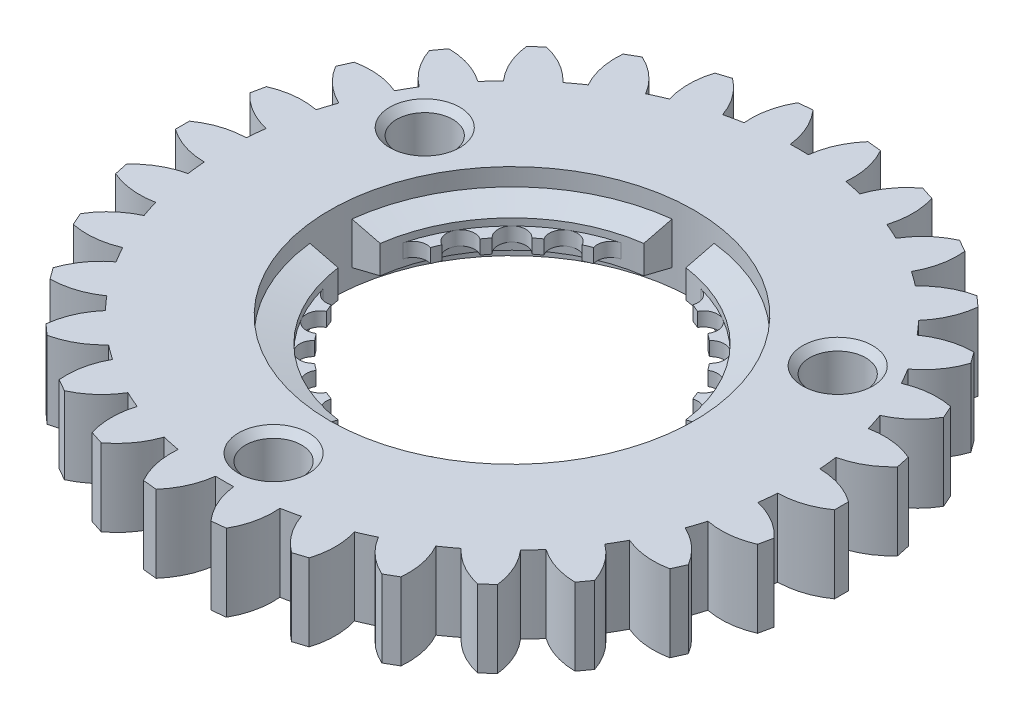
SolidWorks part; units mm, degrees
ref_plane "前视基准面" through (0, 0, 0) normal (0, 0, 1) x (1, 0, 0)
ref_plane "上视基准面" through (0, 0, 0) normal (0, 1, 0) x (1, 0, 0)
ref_plane "右视基准面" through (0, 0, 0) normal (1, 0, 0) x (0, 0, -1)
sketch "草图1" plane through (0, 0, 0) normal (0, 1, 0) x (1, 0, 0)
  circle A0 centre (0, 0) radius 20.5
  dimension "D1" = 41
extrude "凸台-拉伸1" add sketch "草图1" along normal blind 5.5
sketch "草图2" plane through (0, 0, 0) normal (0, 1, 0) x (1, 0, 0)
  line L0 (0, 0) -> (-20.5, 0) construction
  line L1 (-20.5, 0) -> (-23.5, 0) construction
  line L2 (-23.5, 0.5) -> (-23.5, -0.5)
  line L3 (-20.5, 0) -> (-20.5, -1.5) construction
  line L4 (-22, 0) -> (-22, -1.25) construction
  line L5 (-22.8825, 5.375) -> (-23.0904, 4.3969)
  line L6 (-21.2649, 10.0151) -> (-21.6717, 9.1015)
  line L7 (-18.718, 14.2175) -> (-19.3058, 13.4084)
  line L8 (-15.353, 17.7985) -> (-16.0961, 17.1293)
  line L9 (-11.317, 20.6016) -> (-12.183, 20.1016)
  line L10 (-6.7864, 22.5043) -> (-7.7374, 22.1953)
  line L11 (-1.9592, 23.4235) -> (-2.9537, 23.319)
  line L12 (2.9537, 23.319) -> (1.9592, 23.4235)
  line L13 (7.7374, 22.1953) -> (6.7864, 22.5043)
  line L14 (12.183, 20.1016) -> (11.317, 20.6016)
  line L15 (16.0961, 17.1293) -> (15.353, 17.7985)
  line L16 (19.3058, 13.4084) -> (18.718, 14.2175)
  line L17 (21.6717, 9.1015) -> (21.2649, 10.0151)
  line L18 (23.0904, 4.3969) -> (22.8825, 5.375)
  line L19 (23.5, -0.5) -> (23.5, 0.5)
  line L20 (22.8825, -5.375) -> (23.0904, -4.3969)
  line L21 (21.2649, -10.0151) -> (21.6717, -9.1015)
  line L22 (18.718, -14.2175) -> (19.3058, -13.4084)
  line L23 (15.353, -17.7985) -> (16.0961, -17.1293)
  line L24 (11.317, -20.6016) -> (12.183, -20.1016)
  line L25 (6.7864, -22.5043) -> (7.7374, -22.1953)
  line L26 (1.9592, -23.4235) -> (2.9537, -23.319)
  line L27 (-2.9537, -23.319) -> (-1.9592, -23.4235)
  line L28 (-7.7374, -22.1953) -> (-6.7864, -22.5043)
  line L29 (-12.183, -20.1016) -> (-11.317, -20.6016)
  line L30 (-16.0961, -17.1293) -> (-15.353, -17.7985)
  line L31 (-19.3058, -13.4084) -> (-18.718, -14.2175)
  line L32 (-21.6717, -9.1015) -> (-21.2649, -10.0151)
  line L33 (-23.0904, -4.3969) -> (-22.8825, -5.375)
  arc A0 (-20.445, 1.5) -> (-20.445, -1.5) centre (0, 0) ccw
  arc A1 (-23.5, -0.5) -> (-20.445, -1.5) centre (-20.3801, 3.8648) ccw
  arc A2 (-23.5, 0.5) -> (-20.445, 1.5) centre (-20.3801, -3.8648) cw
  arc A3 (-22.8825, 5.375) -> (-19.6864, 5.718) centre (-20.7383, 0.4569) cw
  arc A4 (-23.0904, 4.3969) -> (-20.3101, 2.7835) centre (-19.1312, 8.0176) ccw
  arc A5 (-19.6864, 5.718) -> (-20.3101, 2.7835) centre (0, 0) ccw
  arc A6 (-21.2649, 10.0151) -> (-18.0674, 9.6861) centre (-20.1901, 4.7586) cw
  arc A7 (-21.6717, 9.1015) -> (-19.2876, 6.9454) centre (-17.0462, 11.82) ccw
  arc A8 (-18.0674, 9.6861) -> (-19.2876, 6.9454) centre (0, 0) ccw
  arc A9 (-18.718, 14.2175) -> (-15.6587, 13.2308) centre (-18.7595, 8.8524) cw
  arc A10 (-19.3058, 13.4084) -> (-17.4221, 10.8038) centre (-14.2161, 15.1058) ccw
  arc A11 (-15.6587, 13.2308) -> (-17.4221, 10.8038) centre (0, 0) ccw
  arc A12 (-15.353, 17.7985) -> (-12.5657, 16.1973) centre (-16.5091, 12.5593) cw
  arc A13 (-16.0961, 17.1293) -> (-14.7951, 14.1899) centre (-10.7648, 17.7314) ccw
  arc A14 (-12.5657, 16.1973) -> (-14.7951, 14.1899) centre (0, 0) ccw
  arc A15 (-11.317, 20.6016) -> (-8.9235, 18.4559) centre (-13.5371, 15.7172) cw
  arc A16 (-12.183, 20.1016) -> (-11.5216, 16.9559) centre (-6.843, 19.5821) ccw
  arc A17 (-8.9235, 18.4559) -> (-11.5216, 16.9559) centre (0, 0) ccw
  arc A18 (-6.7864, 22.5043) -> (-4.8913, 19.9079) centre (-9.9735, 18.1883) cw
  arc A19 (-7.7374, 22.1953) -> (-7.7445, 18.9809) centre (-2.6221, 20.5769) ccw
  arc A20 (-4.8913, 19.9079) -> (-7.7445, 18.9809) centre (0, 0) ccw
  arc A21 (-1.9592, 23.4235) -> (-0.6453, 20.4898) centre (-5.974, 19.8644) cw
  arc A22 (-2.9537, 23.319) -> (-3.6289, 20.1763) centre (1.7134, 20.6724) ccw
  arc A23 (-0.6453, 20.4898) -> (-3.6289, 20.1763) centre (0, 0) ccw
  arc A24 (2.9537, 23.319) -> (3.6289, 20.1763) centre (-1.7134, 20.6724) cw
  arc A25 (1.9592, 23.4235) -> (0.6453, 20.4898) centre (5.974, 19.8644) ccw
  arc A26 (3.6289, 20.1763) -> (0.6453, 20.4898) centre (0, 0) ccw
  arc A27 (7.7374, 22.1953) -> (7.7445, 18.9809) centre (2.6221, 20.5769) cw
  arc A28 (6.7864, 22.5043) -> (4.8913, 19.9079) centre (9.9735, 18.1883) ccw
  arc A29 (7.7445, 18.9809) -> (4.8913, 19.9079) centre (0, 0) ccw
  arc A30 (12.183, 20.1016) -> (11.5216, 16.9559) centre (6.843, 19.5821) cw
  arc A31 (11.317, 20.6016) -> (8.9235, 18.4559) centre (13.5371, 15.7172) ccw
  arc A32 (11.5216, 16.9559) -> (8.9235, 18.4559) centre (0, 0) ccw
  arc A33 (16.0961, 17.1293) -> (14.7951, 14.1899) centre (10.7648, 17.7314) cw
  arc A34 (15.353, 17.7985) -> (12.5657, 16.1973) centre (16.5091, 12.5593) ccw
  arc A35 (14.7951, 14.1899) -> (12.5657, 16.1973) centre (0, 0) ccw
  arc A36 (19.3058, 13.4084) -> (17.4221, 10.8038) centre (14.2161, 15.1058) cw
  arc A37 (18.718, 14.2175) -> (15.6587, 13.2308) centre (18.7595, 8.8524) ccw
  arc A38 (17.4221, 10.8038) -> (15.6587, 13.2308) centre (0, 0) ccw
  arc A39 (21.6717, 9.1015) -> (19.2876, 6.9454) centre (17.0462, 11.82) cw
  arc A40 (21.2649, 10.0151) -> (18.0674, 9.6861) centre (20.1901, 4.7586) ccw
  arc A41 (19.2876, 6.9454) -> (18.0674, 9.6861) centre (0, 0) ccw
  arc A42 (23.0904, 4.3969) -> (20.3101, 2.7835) centre (19.1312, 8.0176) cw
  arc A43 (22.8825, 5.375) -> (19.6864, 5.718) centre (20.7383, 0.4569) ccw
  arc A44 (20.3101, 2.7835) -> (19.6864, 5.718) centre (0, 0) ccw
  arc A45 (23.5, -0.5) -> (20.445, -1.5) centre (20.3801, 3.8648) cw
  arc A46 (23.5, 0.5) -> (20.445, 1.5) centre (20.3801, -3.8648) ccw
  arc A47 (20.445, -1.5) -> (20.445, 1.5) centre (0, 0) ccw
  arc A48 (22.8825, -5.375) -> (19.6864, -5.718) centre (20.7383, -0.4569) cw
  arc A49 (23.0904, -4.3969) -> (20.3101, -2.7835) centre (19.1312, -8.0176) ccw
  arc A50 (19.6864, -5.718) -> (20.3101, -2.7835) centre (0, 0) ccw
  arc A51 (21.2649, -10.0151) -> (18.0674, -9.6861) centre (20.1901, -4.7586) cw
  arc A52 (21.6717, -9.1015) -> (19.2876, -6.9454) centre (17.0462, -11.82) ccw
  arc A53 (18.0674, -9.6861) -> (19.2876, -6.9454) centre (0, 0) ccw
  arc A54 (18.718, -14.2175) -> (15.6587, -13.2308) centre (18.7595, -8.8524) cw
  arc A55 (19.3058, -13.4084) -> (17.4221, -10.8038) centre (14.2161, -15.1058) ccw
  arc A56 (15.6587, -13.2308) -> (17.4221, -10.8038) centre (0, 0) ccw
  arc A57 (15.353, -17.7985) -> (12.5657, -16.1973) centre (16.5091, -12.5593) cw
  arc A58 (16.0961, -17.1293) -> (14.7951, -14.1899) centre (10.7648, -17.7314) ccw
  arc A59 (12.5657, -16.1973) -> (14.7951, -14.1899) centre (0, 0) ccw
  arc A60 (11.317, -20.6016) -> (8.9235, -18.4559) centre (13.5371, -15.7172) cw
  arc A61 (12.183, -20.1016) -> (11.5216, -16.9559) centre (6.843, -19.5821) ccw
  arc A62 (8.9235, -18.4559) -> (11.5216, -16.9559) centre (0, 0) ccw
  arc A63 (6.7864, -22.5043) -> (4.8913, -19.9079) centre (9.9735, -18.1883) cw
  arc A64 (7.7374, -22.1953) -> (7.7445, -18.9809) centre (2.6221, -20.5769) ccw
  arc A65 (4.8913, -19.9079) -> (7.7445, -18.9809) centre (0, 0) ccw
  arc A66 (1.9592, -23.4235) -> (0.6453, -20.4898) centre (5.974, -19.8644) cw
  arc A67 (2.9537, -23.319) -> (3.6289, -20.1763) centre (-1.7134, -20.6724) ccw
  arc A68 (0.6453, -20.4898) -> (3.6289, -20.1763) centre (0, 0) ccw
  arc A69 (-2.9537, -23.319) -> (-3.6289, -20.1763) centre (1.7134, -20.6724) cw
  arc A70 (-1.9592, -23.4235) -> (-0.6453, -20.4898) centre (-5.974, -19.8644) ccw
  arc A71 (-3.6289, -20.1763) -> (-0.6453, -20.4898) centre (0, 0) ccw
  arc A72 (-7.7374, -22.1953) -> (-7.7445, -18.9809) centre (-2.6221, -20.5769) cw
  arc A73 (-6.7864, -22.5043) -> (-4.8913, -19.9079) centre (-9.9735, -18.1883) ccw
  arc A74 (-7.7445, -18.9809) -> (-4.8913, -19.9079) centre (0, 0) ccw
  arc A75 (-12.183, -20.1016) -> (-11.5216, -16.9559) centre (-6.843, -19.5821) cw
  arc A76 (-11.317, -20.6016) -> (-8.9235, -18.4559) centre (-13.5371, -15.7172) ccw
  arc A77 (-11.5216, -16.9559) -> (-8.9235, -18.4559) centre (0, 0) ccw
  arc A78 (-16.0961, -17.1293) -> (-14.7951, -14.1899) centre (-10.7648, -17.7314) cw
  arc A79 (-15.353, -17.7985) -> (-12.5657, -16.1973) centre (-16.5091, -12.5593) ccw
  arc A80 (-14.7951, -14.1899) -> (-12.5657, -16.1973) centre (0, 0) ccw
  arc A81 (-19.3058, -13.4084) -> (-17.4221, -10.8038) centre (-14.2161, -15.1058) cw
  arc A82 (-18.718, -14.2175) -> (-15.6587, -13.2308) centre (-18.7595, -8.8524) ccw
  arc A83 (-17.4221, -10.8038) -> (-15.6587, -13.2308) centre (0, 0) ccw
  arc A84 (-21.6717, -9.1015) -> (-19.2876, -6.9454) centre (-17.0462, -11.82) cw
  arc A85 (-21.2649, -10.0151) -> (-18.0674, -9.6861) centre (-20.1901, -4.7586) ccw
  arc A86 (-19.2876, -6.9454) -> (-18.0674, -9.6861) centre (0, 0) ccw
  arc A87 (-23.0904, -4.3969) -> (-20.3101, -2.7835) centre (-19.1312, -8.0176) cw
  arc A88 (-22.8825, -5.375) -> (-19.6864, -5.718) centre (-20.7383, -0.4569) ccw
  arc A89 (-20.3101, -2.7835) -> (-19.6864, -5.718) centre (0, 0) ccw
  point P190 (0, 0)
  dimension "D1" = 30
  dimension "D2" = 0.5
  dimension "D4" = 1.25
extrude "凸台-拉伸2" add sketch "草图2" along normal blind 5.5
sketch "草图3" plane through (0, 5.5, 0) normal (0, 1, 0) x (1, 0, 0)
  circle A0 centre (0, 0) radius 13
  dimension "D1" = 26
extrude "切除-拉伸1" cut sketch "草图3" against normal blind 1.25
sketch "草图4" plane through (0, 0, 0) normal (0, -1, 0) x (1, 0, 0)
  circle A0 centre (0, 0) radius 13
  dimension "D1" = 26
extrude "切除-拉伸2" cut sketch "草图4" against normal blind 1.25
sketch "草图5" plane through (0, 0, 0) normal (0, 0, 1) x (1, 0, 0)
  line L0 (0, 2.75) -> (0, 0) construction
  line L1 (0, 2.75) -> (-13, 2.75) construction
  line L2 (-13, 2.75) -> (-13, 4.25) construction
  line L3 (-13, 4.25) -> (-11, 3.75)
  line L4 (-11, 3.75) -> (-11, 2.75) construction
  line L5 (-13, 4.25) -> (0, 4.25)
  line L6 (0, 4.25) -> (0, 3.75)
  line L7 (-11, 3.75) -> (0, 3.75)
  line L8 (-13, 1.25) -> (-11, 1.75)
  line L9 (-11, 1.75) -> (0, 1.75)
  line L10 (-13, 1.25) -> (0, 1.25)
  line L11 (0, 1.75) -> (0, 1.25)
  dimension "D1" = 2.75
  dimension "D2" = 13
  dimension "D3" = 1.5
  dimension "D4" = 1
  dimension "D5" = 13
  dimension "D6" = 11
revolve "切除-旋转1" cut sketch "草图5" angle 360 about L0
sketch "草图6" plane through (0, 3.75, 0) normal (0, 1, 0) x (1, 0, 0)
  circle A0 centre (0, 0) radius 11
extrude "切除-拉伸3" cut sketch "草图6" against normal blind 0.5
sketch "草图7" plane through (0, 1.75, 0) normal (0, -1, 0) x (1, 0, 0)
  circle A0 centre (0, 0) radius 11
extrude "切除-拉伸4" cut sketch "草图7" against normal blind 0.5
sketch "草图8" plane through (0, 2.25, 0) normal (0, -1, 0) x (1, 0, 0)
  circle A0 centre (0, 0) radius 10
  dimension "D1" = 20
extrude "切除-拉伸5" cut sketch "草图8" against normal through all
sketch "草图10" plane through (0, 2.25, 0) normal (0, -1, 0) x (1, 0, 0)
  line L0 (0, 0) -> (0, -10) construction
  line L1 (0, 0) -> (-10, 0) construction
  line L2 (0, 0) -> (10, 0) construction
  line L3 (0, 0) -> (0, 10) construction
  circle A0 centre (0, 0) radius 10 construction
  arc A1 (3.54, -9.3525) -> (-3.54, -9.3525) centre (0, 0) cw
  arc A2 (-3.54, -9.3525) -> (-2.847, -10.6252) centre (-2.5882, -9.6593) ccw
  circle A3 centre (-5, -8.6603) radius 1
  circle A4 centre (-7.0711, -7.0711) radius 1
  circle A5 centre (-8.6603, -5) radius 1
  arc A6 (-9.3525, -3.54) -> (-9.3525, 3.54) centre (0, 0) cw
  arc A7 (-9.3525, 3.54) -> (-10.6252, 2.847) centre (-9.6593, 2.5882) ccw
  arc A8 (-10.6252, 2.847) -> (-10.6252, -2.847) centre (0, 0) ccw
  circle A9 centre (-8.6603, 5) radius 1
  circle A10 centre (-7.0711, 7.0711) radius 1
  circle A11 centre (-5, 8.6603) radius 1
  arc A12 (-10.6252, -2.847) -> (-9.3525, -3.54) centre (-9.6593, -2.5882) ccw
  arc A13 (-3.54, 9.3525) -> (3.54, 9.3525) centre (0, 0) cw
  arc A14 (3.54, 9.3525) -> (2.847, 10.6252) centre (2.5882, 9.6593) ccw
  circle A15 centre (5, 8.6603) radius 1
  circle A16 centre (7.0711, 7.0711) radius 1
  circle A17 centre (8.6603, 5) radius 1
  arc A18 (2.847, 10.6252) -> (-2.847, 10.6252) centre (0, 0) ccw
  arc A19 (-2.847, 10.6252) -> (-3.54, 9.3525) centre (-2.5882, 9.6593) ccw
  arc A20 (9.3525, 3.54) -> (9.3525, -3.54) centre (0, 0) cw
  circle A21 centre (8.6603, -5) radius 1
  circle A22 centre (7.0711, -7.0711) radius 1
  circle A23 centre (5, -8.6603) radius 1
  arc A24 (2.847, -10.6252) -> (3.54, -9.3525) centre (2.5882, -9.6593) ccw
  arc A25 (-2.847, -10.6252) -> (2.847, -10.6252) centre (0, 0) ccw
  circle A26 centre (0, 0) radius 11 construction
  arc A27 (9.3525, -3.54) -> (10.6252, -2.847) centre (9.6593, -2.5882) ccw
  arc A37 (10.6252, -2.847) -> (10.6252, 2.847) centre (0, 0) ccw
  arc A38 (10.6252, 2.847) -> (9.3525, 3.54) centre (9.6593, 2.5882) ccw
  point P55 (0, 0)
  point P81 (0, 0)
  dimension "D1" = 4
extrude "切除-拉伸6" cut sketch "草图10" against normal through all
sketch "草图11" plane through (0, 0, 0) normal (0, -1, 0) x (1, 0, 0)
  line L0 (0, 0) -> (0, 13) construction
  line L1 (0, 0) -> (0, 11) construction
  line L2 (-1.5, 12.9132) -> (-1.5, 10.8972)
  line L3 (1.5, 12.9132) -> (1.5, 10.8972)
  line L4 (12.9132, 1.5) -> (10.8972, 1.5)
  line L5 (12.9132, -1.5) -> (10.8972, -1.5)
  line L6 (1.5, -12.9132) -> (1.5, -10.8972)
  line L7 (-1.5, -12.9132) -> (-1.5, -10.8972)
  line L8 (-12.9132, -1.5) -> (-10.8972, -1.5)
  line L9 (-12.9132, 1.5) -> (-10.8972, 1.5)
  circle A0 centre (0, 0) radius 13 construction
  circle A1 centre (0, 0) radius 13 construction
  arc A2 (1.5, 12.9132) -> (-1.5, 12.9132) centre (0, 0) ccw
  arc A3 (1.5, 10.8972) -> (-1.5, 10.8972) centre (0, 0) ccw
  arc A4 (12.9132, -1.5) -> (12.9132, 1.5) centre (0, 0) ccw
  arc A5 (10.8972, -1.5) -> (10.8972, 1.5) centre (0, 0) ccw
  arc A6 (-1.5, -12.9132) -> (1.5, -12.9132) centre (0, 0) ccw
  arc A7 (-1.5, -10.8972) -> (1.5, -10.8972) centre (0, 0) ccw
  arc A8 (-12.9132, 1.5) -> (-12.9132, -1.5) centre (0, 0) ccw
  arc A9 (-10.8972, 1.5) -> (-10.8972, -1.5) centre (0, 0) ccw
  point P27 (0, 0)
  dimension "D1" = 11
  dimension "D2" = 1.5
  dimension "D3" = 4
extrude "切除-拉伸7" cut sketch "草图11" against normal through all
sketch "草图12" plane through (0, 0, 0) normal (0, -1, 0) x (1, 0, 0)
  line L0 (0, 0) -> (0, 17) construction
  circle A0 centre (0, 0) radius 17 construction
  circle A1 centre (0, 17) radius 2
  circle A2 centre (14.7224, -8.5) radius 2
  circle A3 centre (-14.7224, -8.5) radius 2
  point P11 (0, 0)
  dimension "D1" = 34
  dimension "D2" = 4
  dimension "D3" = 3
extrude "切除-拉伸8" cut sketch "草图12" against normal through all
sketch "草图13" plane through (0, 0, 0) normal (0, -1, 0) x (1, 0, 0)
  line L0 (0, 0) -> (0, 17) construction
  line L1 (0, 0) -> (6.3801, 15.7574) construction
  line L2 (0, 0) -> (14.7224, -8.5) construction
  line L3 (0, 0) -> (16.8363, -2.3533) construction
  arc A0 (14.7224, -8.5) -> (0, 17) centre (0, 0) ccw construction
  arc A1 (14.8556, -2.0765) -> (5.6295, 13.9035) centre (0, 0) ccw
  arc A2 (18.8171, -2.6302) -> (7.1307, 17.6112) centre (0, 0) ccw
  arc A3 (7.1307, 17.6112) -> (5.6295, 13.9035) centre (6.3801, 15.7574) ccw
  arc A4 (14.8556, -2.0765) -> (18.8171, -2.6302) centre (16.8363, -2.3533) ccw
  arc A5 (-9.2261, -11.8271) -> (9.2261, -11.8271) centre (0, 0) ccw
  arc A6 (-11.6864, -14.981) -> (11.6864, -14.981) centre (0, 0) ccw
  arc A7 (11.6864, -14.981) -> (9.2261, -11.8271) centre (10.4562, -13.404) ccw
  arc A8 (-9.2261, -11.8271) -> (-11.6864, -14.981) centre (-10.4562, -13.404) ccw
  arc A9 (-5.6295, 13.9035) -> (-14.8556, -2.0765) centre (0, 0) ccw
  arc A10 (-7.1307, 17.6112) -> (-18.8171, -2.6302) centre (0, 0) ccw
  arc A11 (-18.8171, -2.6302) -> (-14.8556, -2.0765) centre (-16.8363, -2.3533) ccw
  arc A12 (-5.6295, 13.9035) -> (-7.1307, 17.6112) centre (-6.3801, 15.7574) ccw
  point P24 (0, 0)
  dimension "D1" = 34
  dimension "D2" = 30
  dimension "D3" = 3
  dimension "D4" = 240
  dimension "D5" = 6.5
  dimension "D6" = 6.5
extrude "切除-拉伸9" cut sketch "草图13" against normal blind 4
chamfer "倒角1" distance 0.5 angle 45 6 edges at (-14.7224, 5.5, -10.5) (14.7224, 5.5, -10.5) (0, 5.5, 15) (14.7224, 0, -10.5) (-14.7224, 0, -10.5) (0, 0, 15)
